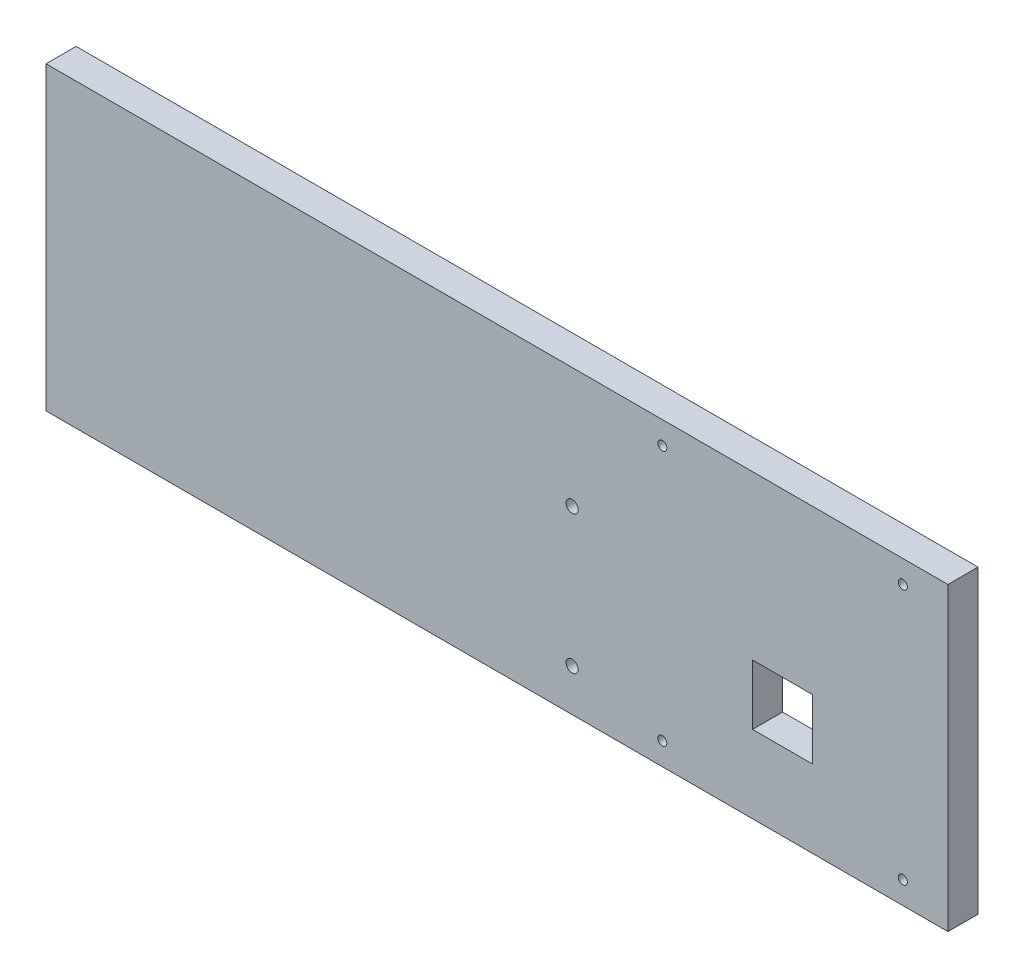
SolidWorks part; units mm, degrees
material "Faia"
ref_plane "Plano frontal" through (0, 0, 0) normal (0, 0, 1) x (1, 0, 0)
ref_plane "Plano superior" through (0, 0, 0) normal (0, 1, 0) x (1, 0, 0)
ref_plane "Plano direito" through (0, 0, 0) normal (1, 0, 0) x (0, 0, -1)
sketch "Esboço1" plane through (0, 0, 0) normal (0, 0, 1) x (1, 0, 0)
  line L0 (150, 0) -> (-150, 0) construction
  line L1 (-150, 50) -> (150, 50)
  line L2 (-150, 50) -> (-150, -50)
  line L3 (-150, -50) -> (150, -50)
  line L4 (150, 50) -> (150, -50)
  line L5 (-150, 50) -> (150, -50) construction
  line L6 (-150, -50) -> (150, 50) construction
  line L7 (70, 0) -> (-230, 0) construction
  line L8 (25, -36) -> (25, 10) construction
  line L9 (55, 42.5) -> (55, -42.5) construction
  line L10 (135, 42.5) -> (55, 42.5) construction
  line L11 (55, -42.5) -> (135, -42.5) construction
  line L13 (85, -4.25) -> (105, -4.25)
  line L14 (85, -4.25) -> (85, -24.25)
  line L15 (85, -24.25) -> (105, -24.25)
  line L16 (105, -4.25) -> (105, -24.25)
  line L17 (85, -4.25) -> (105, -24.25) construction
  line L18 (85, -24.25) -> (105, -4.25) construction
  circle A0 centre (135, 42.5) radius 1.5
  circle A1 centre (135, -42.5) radius 1.5
  circle A2 centre (55, -42.5) radius 1.5
  circle A3 centre (55, 42.5) radius 1.5
  circle A4 centre (25, 10) radius 2
  circle A5 centre (25, -36) radius 2
  point P0 (0, 0)
  point P21 (5, 0)
  point P23 (95, -14.25)
  point P28 (95, -42.5)
  point P29 (55, 0)
  dimension "D5" = 3
  dimension "D8" = 4
  dimension "D1" = 300
  dimension "D2" = 100
  dimension "D3" = 15
  dimension "D4" = 85
  dimension "D7" = 80
  dimension "D9" = 46
  dimension "D10" = 125
  dimension "D11" = 40
  dimension "D13" = 20
  dimension "D14" = 20
  dimension "D15" = 28.25
  dimension "D6" = 2
extrude "Ressalto-extrusão1" add sketch "Esboço1" along normal blind 10 contours L4 L1 L2 L3 A3 A1 A0 A2 region at (-1.3983, 0.204, 0)
